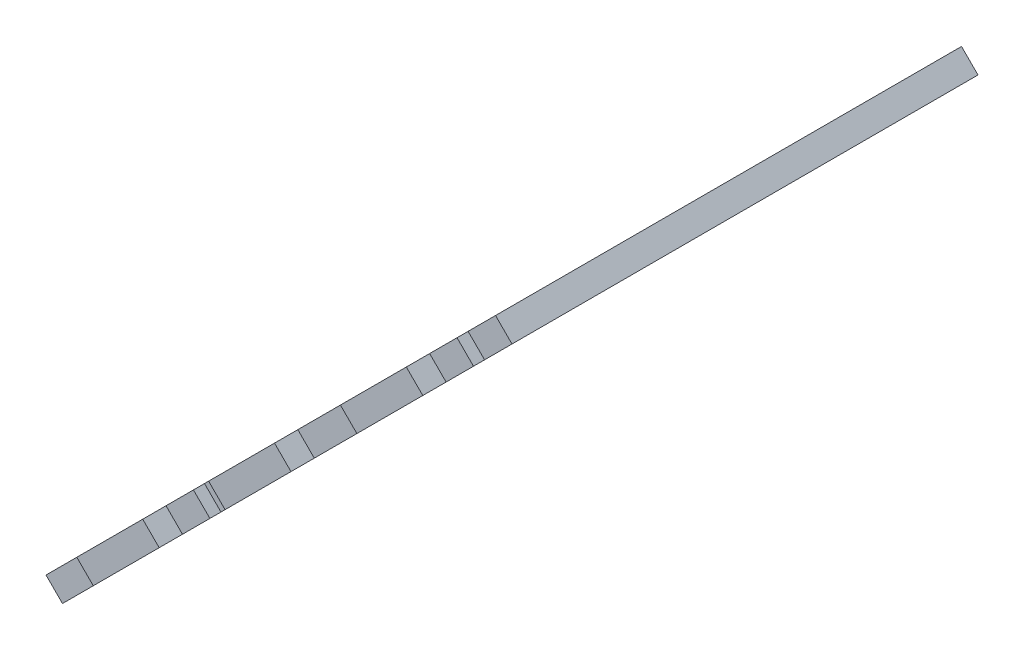
SolidWorks part; units mm, degrees
ref_plane "Front Plane" through (0, 0, 0) normal (0, 0, 1) x (1, 0, 0)
ref_plane "Top Plane" through (0, 0, 0) normal (0, 1, 0) x (1, 0, 0)
ref_plane "Right Plane" through (0, 0, 0) normal (1, 0, 0) x (0, 0, -1)
sketch "Sketch1" plane through (0, 0, 0) normal (0, 0, 1) x (1, 0, 0)
  line L0 (0, 127) -> (4.4901, 122.5099)
  line L1 (0, 127) -> (-122.5099, 4.4901)
  line L2 (4.4901, 122.5099) -> (-118.0197, 0)
  line L3 (-122.5099, 4.4901) -> (-118.0197, 0)
  line L4 (127, 0) -> (0, 127) construction
  line L5 (4.4901, -122.5099) -> (-122.5099, 4.4901) construction
  dimension "D1" = 6.35
extrude "Boss-Extrude1" add sketch "Sketch1" along normal up to surface (127 mm away)
sketch "Sketch2" plane through (-59.0099, -59.0099, 0) normal (-0.7071, -0.7071, 0) x (0, 0, 1)
  line L0 (127, 83.4526) -> (0, 83.4526) construction
  line L1 (25.4, 83.4526) -> (50.8, 83.4526)
  line L2 (25.4, 83.4526) -> (25.4, 89.8026)
  line L3 (25.4, 89.8026) -> (50.8, 89.8026)
  line L4 (50.8, 83.4526) -> (50.8, 89.8026)
  line L5 (127, 89.8026) -> (0, 89.8026) construction
  dimension "D1" = 25.4
  dimension "D2" = 25.4
extrude "Boss-Extrude2" add sketch "Sketch2" along normal blind 6.35
pattern_linear "LPattern1" count 2 spacing 50.8 along (0, 0, 1) of "Boss-Extrude2"
sketch "Sketch3" plane through (-59.0099, 59.0099, 0) normal (0.7071, -0.7071, 0) x (0, 0, -1)
  line L0 (-35.9664, -83.4526) -> (-40.2336, -89.8026) construction
  line L1 (-25.4, -89.8026) -> (-50.8, -89.8026) construction
  line L2 (-40.2336, -83.4526) -> (-40.2336, -89.8026) construction
  line L3 (-40.2336, -83.4526) -> (-35.9664, -89.8026) construction
  line L4 (-35.9664, -83.4526) -> (-35.9664, -89.8026) construction
  line L5 (-86.8461, -83.4526) -> (-91.1133, -89.8026) construction
  line L6 (-76.2, -89.8026) -> (-101.6, -89.8026) construction
  line L7 (-91.1133, -83.4526) -> (-91.1133, -89.8026) construction
  line L8 (-91.1133, -83.4526) -> (-86.8461, -89.8026) construction
  circle A0 centre (-38.1, -86.6276) radius 2.0955
  circle A1 centre (-88.9797, -86.6276) radius 2.0955
  dimension "D1" = 4.191
extrude "Cut-Extrude1" cut sketch "Sketch3" against normal blind 6.35
sketch "Sketch4" plane through (-63.5, 63.5, 0) normal (-0.7071, 0.7071, 0) x (0, 0, 1)
  line L0 (12.7, -83.4526) -> (12.7, -46.5697) construction
  line L1 (25.4, -83.4526) -> (0, -83.4526) construction
  line L2 (114.3, -83.4526) -> (114.3, -49.3378) construction
  line L3 (127, -83.4526) -> (101.6, -83.4526) construction
  line B0 (10.5664, -83.4526) -> (14.8336, -83.4526)
  line B1 (14.8336, -71.5146) -> (17.145, -71.5146)
  line B2 (17.145, -71.5146) -> (17.145, -74.6896)
  line B3 (17.145, -74.6896) -> (14.8336, -74.6896)
  line B4 (14.8336, -74.6896) -> (14.8336, -83.4526)
  line B5 (14.8336, -71.5146) -> (14.8336, -68.2126)
  line B6 (14.8336, -68.2126) -> (10.5664, -68.2126)
  line B7 (10.5664, -71.5146) -> (10.5664, -68.2126)
  line B8 (10.5664, -74.6896) -> (10.5664, -83.4526)
  line B9 (8.255, -74.6896) -> (10.5664, -74.6896)
  line B10 (8.255, -71.5146) -> (8.255, -74.6896)
  line B11 (10.5664, -71.5146) -> (8.255, -71.5146)
  line B12 (112.1664, -83.4526) -> (116.4336, -83.4526)
  line B13 (116.4336, -71.5146) -> (118.745, -71.5146)
  line B14 (118.745, -71.5146) -> (118.745, -74.6896)
  line B15 (118.745, -74.6896) -> (116.4336, -74.6896)
  line B16 (116.4336, -74.6896) -> (116.4336, -83.4526)
  line B17 (116.4336, -71.5146) -> (116.4336, -68.2126)
  line B18 (116.4336, -68.2126) -> (112.1664, -68.2126)
  line B19 (112.1664, -71.5146) -> (112.1664, -68.2126)
  line B20 (112.1664, -74.6896) -> (112.1664, -83.4526)
  line B21 (109.855, -74.6896) -> (112.1664, -74.6896)
  line B22 (109.855, -71.5146) -> (109.855, -74.6896)
  line B23 (112.1664, -71.5146) -> (109.855, -71.5146)
sketch_block_instance "TSlot-1"
sketch_block "TSlot" parameters "D1"=3.302, "D2"=3.175
sketch_block_instance "TSlot-3"
extrude "Cut-Extrude2" cut sketch "Sketch4" against normal blind 6.35
sketch "Sketch6" plane through (0, 0, 0) normal (0, 0, -1) x (-1, 0, 0)
  line L0 (13.4704, 104.5494) -> (17.9605, 109.0395)
  line L1 (118.0197, 0) -> (-4.4901, 122.5099) construction
  line L2 (0, 127) -> (122.5099, 4.4901) construction
  line L3 (17.9605, 109.0395) -> (35.921, 91.079)
  line L4 (35.921, 91.079) -> (31.4309, 86.5888)
  line L5 (31.4309, 86.5888) -> (13.4704, 104.5494)
  dimension "D1" = 25.4
  dimension "D2" = 25.4
extrude "Boss-Extrude4" add sketch "Sketch6" along normal blind 6.35
pattern_linear "LPattern3" count 3 spacing 50.8 along (-0.7071, -0.7071, 0) of "Boss-Extrude4"
sketch "Sketch7" plane through (0, 0, 127) normal (0, 0, 1) x (1, 0, 0)
  line L0 (-17.9605, 109.0395) -> (-13.4704, 104.5494)
  line L1 (-122.5099, 4.4901) -> (0, 127) construction
  line L2 (4.4901, 122.5099) -> (-118.0197, 0) construction
  line L3 (-13.4704, 104.5494) -> (-31.4309, 86.5888)
  line L4 (-31.4309, 86.5888) -> (-35.921, 91.079)
  line L5 (-35.921, 91.079) -> (-17.9605, 109.0395)
  dimension "D1" = 25.4
  dimension "D2" = 25.4
extrude "Boss-Extrude5" add sketch "Sketch7" along normal blind 6.35
pattern_linear "LPattern4" count 3 spacing 50.8 along (-0.7071, -0.7071, 0) of "Boss-Extrude5"
sketch "Sketch8" plane through (-63.5, 63.5, 0) normal (-0.7071, 0.7071, 0) x (0, 0, 1)
  line L0 (0, 89.8026) -> (0, 64.4026) construction
  line L1 (127, 89.8026) -> (127, -89.8026) construction
  line L2 (0, -24.4974) -> (10.2536, -24.4974) construction
  line L3 (0, -11.7974) -> (0, -37.1974) construction
  line L4 (0, 77.1026) -> (13.5818, 77.1026) construction
  line L5 (127, 77.1026) -> (104.4683, 77.1026) construction
  line L6 (127, 64.4026) -> (127, 89.8026) construction
  line L7 (127, -24.4974) -> (109.5887, -24.4974) construction
  line L8 (127, -37.1974) -> (127, -11.7974) construction
  line B0 (127, -26.631) -> (127, -22.3638)
  line B1 (115.062, -22.3638) -> (115.062, -20.0524)
  line B2 (115.062, -20.0524) -> (118.237, -20.0524)
  line B3 (118.237, -20.0524) -> (118.237, -22.3638)
  line B4 (118.237, -22.3638) -> (127, -22.3638)
  line B5 (115.062, -22.3638) -> (111.76, -22.3638)
  line B6 (111.76, -22.3638) -> (111.76, -26.631)
  line B7 (115.062, -26.631) -> (111.76, -26.631)
  line B8 (118.237, -26.631) -> (127, -26.631)
  line B9 (118.237, -28.9424) -> (118.237, -26.631)
  line B10 (115.062, -28.9424) -> (118.237, -28.9424)
  line B11 (115.062, -26.631) -> (115.062, -28.9424)
  line B12 (0, 79.2362) -> (0, 74.969)
  line B13 (11.938, 74.969) -> (11.938, 72.6576)
  line B14 (11.938, 72.6576) -> (8.763, 72.6576)
  line B15 (8.763, 72.6576) -> (8.763, 74.969)
  line B16 (8.763, 74.969) -> (0, 74.969)
  line B17 (11.938, 74.969) -> (15.24, 74.969)
  line B18 (15.24, 74.969) -> (15.24, 79.2362)
  line B19 (11.938, 79.2362) -> (15.24, 79.2362)
  line B20 (8.763, 79.2362) -> (0, 79.2362)
  line B21 (8.763, 81.5476) -> (8.763, 79.2362)
  line B22 (11.938, 81.5476) -> (8.763, 81.5476)
  line B23 (11.938, 79.2362) -> (11.938, 81.5476)
  line B24 (0, -22.3638) -> (0, -26.631)
  line B25 (11.938, -26.631) -> (11.938, -28.9424)
  line B26 (11.938, -28.9424) -> (8.763, -28.9424)
  line B27 (8.763, -28.9424) -> (8.763, -26.631)
  line B28 (8.763, -26.631) -> (0, -26.631)
  line B29 (11.938, -26.631) -> (15.24, -26.631)
  line B30 (15.24, -26.631) -> (15.24, -22.3638)
  line B31 (11.938, -22.3638) -> (15.24, -22.3638)
  line B32 (8.763, -22.3638) -> (0, -22.3638)
  line B33 (8.763, -20.0524) -> (8.763, -22.3638)
  line B34 (11.938, -20.0524) -> (8.763, -20.0524)
  line B35 (11.938, -22.3638) -> (11.938, -20.0524)
  line B36 (127, 74.969) -> (127, 79.2362)
  line B37 (115.062, 79.2362) -> (115.062, 81.5476)
  line B38 (115.062, 81.5476) -> (118.237, 81.5476)
  line B39 (118.237, 81.5476) -> (118.237, 79.2362)
  line B40 (118.237, 79.2362) -> (127, 79.2362)
  line B41 (115.062, 79.2362) -> (111.76, 79.2362)
  line B42 (111.76, 79.2362) -> (111.76, 74.969)
  line B43 (115.062, 74.969) -> (111.76, 74.969)
  line B44 (118.237, 74.969) -> (127, 74.969)
  line B45 (118.237, 72.6576) -> (118.237, 74.969)
  line B46 (115.062, 72.6576) -> (118.237, 72.6576)
  line B47 (115.062, 74.969) -> (115.062, 72.6576)
sketch_block_instance "TSlot-4"
sketch_block_instance "TSlot-5"
sketch_block_instance "TSlot-7"
sketch_block_instance "TSlot-8"
extrude "Cut-Extrude3" cut sketch "Sketch8" against normal blind 6.35
